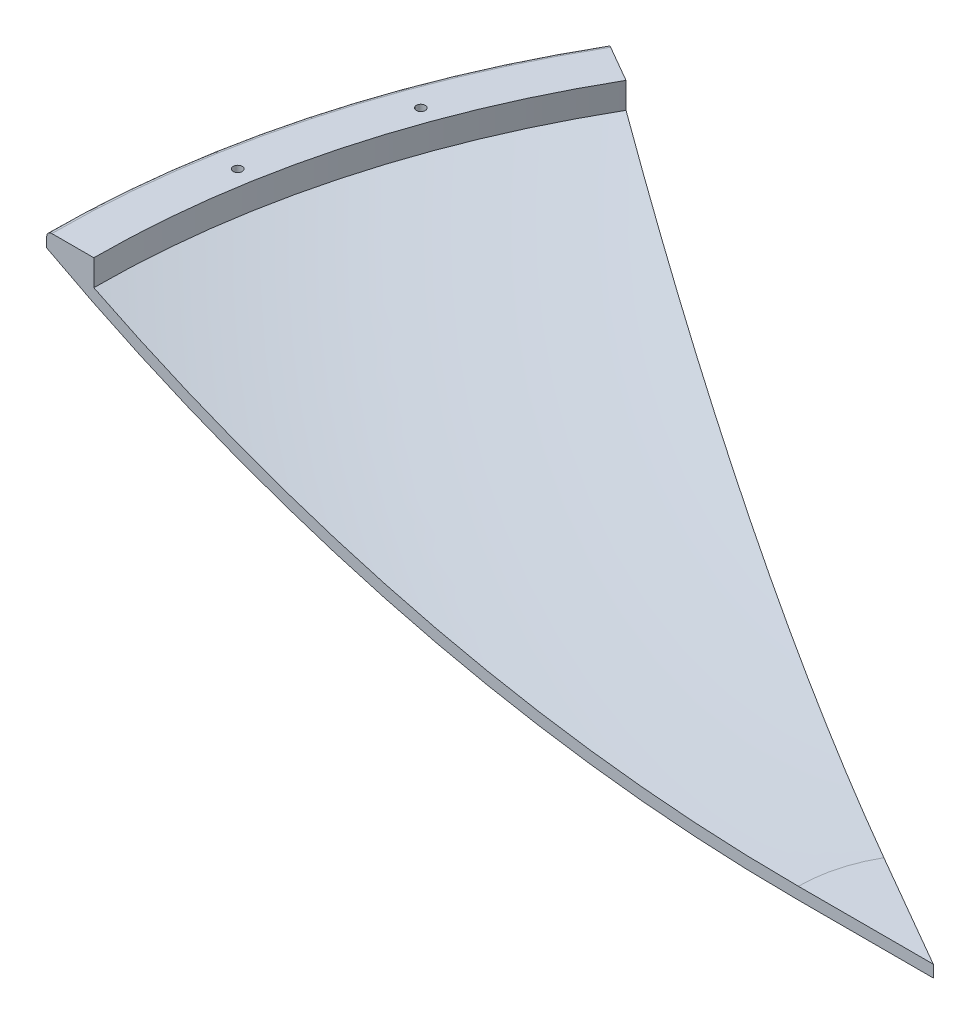
SolidWorks part; units mm, degrees
ref_plane "Front Plane" through (0, 0, 0) normal (0, 0, 1) x (1, 0, 0)
ref_plane "Top Plane" through (0, 0, 0) normal (0, 1, 0) x (1, 0, 0)
ref_plane "Right Plane" through (0, 0, 0) normal (1, 0, 0) x (0, 0, -1)
sketch "Sketch1" plane through (0, 0, 0) normal (0, 0, 1) x (1, 0, 0)
  line L0 (0, -150.7069) -> (-45, -150.7069) construction
  line L1 (-300, -82.3534) -> (-280, -82.3534) construction
  line L2 (-296, -87.5256) -> (-296, -63.1813) construction
  line L3 (0, -150.7069) -> (-45, -150.7069)
  line L4 (-294, -82.3534) -> (-280, -82.3534) construction
  line L5 (-296, -87.5256) -> (-296, -84.3534) construction
  line L6 (-295.7, -87.5256) -> (-295.7, -84.3534)
  line L7 (-294, -82.6534) -> (-280, -82.6534)
  line L8 (-295.7, -87.5256) -> (-295.7, -87.6867)
  line L9 (-280, -82.6534) -> (-280, -91.312)
  line L11 (-45, -146.7069) -> (0, -146.7069)
  line L12 (0, 0) -> (0, -150.7069) construction
  line L13 (0, -146.7069) -> (0, -150.7069)
  line L14 (0, 0) -> (0, -150.7069)
  arc A0 (-294, -82.3534) -> (-296, -84.3534) centre (-294, -84.3534) ccw construction
  arc A1 (-300, -85.3534) -> (-45, -150.7069) centre (-45, 379.457) ccw construction
  arc A2 (-294, -82.3534) -> (-296, -84.3534) centre (-294, -84.3534) ccw construction
  arc A3 (-295.7, -87.6867) -> (-45, -150.7069) centre (-45, 379.457) ccw
  arc A4 (-294, -82.6534) -> (-295.7, -84.3534) centre (-294, -84.3534) ccw
  arc A5 (-280, -91.312) -> (-45, -146.7069) centre (-45, 379.457) ccw
  arc A6 (-293.8085, -84.1622) -> (-45, -146.7069) centre (-45, 379.457) ccw construction
  point P18 (0, 0)
  dimension "D2" = 4
  dimension "D1" = 0.3
revolve "Revolve1" add sketch "Sketch1" angle 30 about L14 region at (-22.5, -147.6726, 0)
sketch "Sketch2" plane through (0, -82.6534, 0) normal (0, 1, 0) x (1, 0, 0)
  circle A0 centre (-281.655, 49.6634) radius 1.5 construction
  circle A1 centre (-268.7521, 97.8178) radius 1.5 construction
  circle A2 centre (-281.655, 49.6634) radius 1.5
  circle A3 centre (-268.7521, 97.8178) radius 1.5
extrude "Cut-Extrude1" cut sketch "Sketch2" against normal through all
